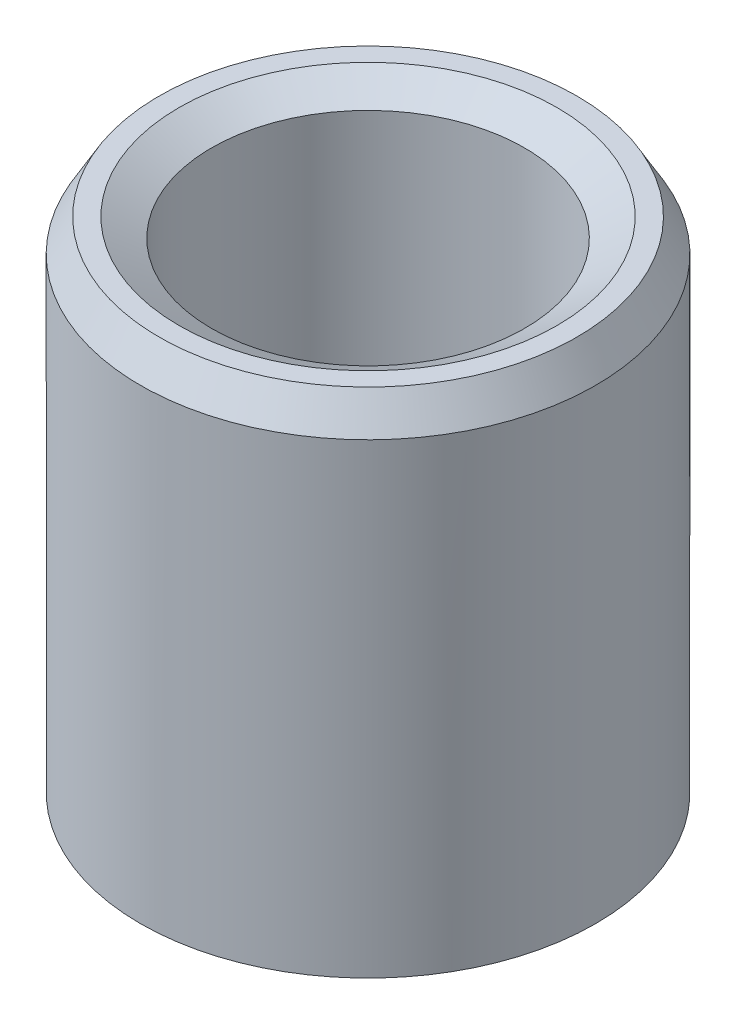
SolidWorks part; units mm, degrees
ref_plane "Front Plane" through (0, 0, 0) normal (0, 0, 1) x (1, 0, 0)
ref_plane "Top Plane" through (0, 0, 0) normal (0, 1, 0) x (1, 0, 0)
ref_plane "Right Plane" through (0, 0, 0) normal (1, 0, 0) x (0, 0, -1)
sketch "Sketch1" plane through (0, 0, 0) normal (0, 1, 0) x (1, 0, 0)
  circle A0 centre (0, 0) radius 20
  dimension "SLEEVE_OD" = 40
extrude "Boss-Extrude1" add sketch "Sketch1" along normal blind 45.4611
sketch "Sketch2" plane through (0, 0, 0) normal (0, 1, 0) x (1, 0, 0)
  circle A0 centre (0, 0) radius 13.7518
  dimension "BORE_D" = 27.5037
extrude "Cut-Extrude1" cut sketch "Sketch2" along normal through all
chamfer "Chamfer1" distance 2.8494 angle 30 4 edges at (0, 45.4611, 13.7518) (0, 0, 13.7518) (0, 0, 20) (0, 45.4611, 20) first distance on face at (0, 45.4611, 13.7518) first distance on face at (0, 0, 13.7518) first distance on face at (0, 45.4611, 20)
